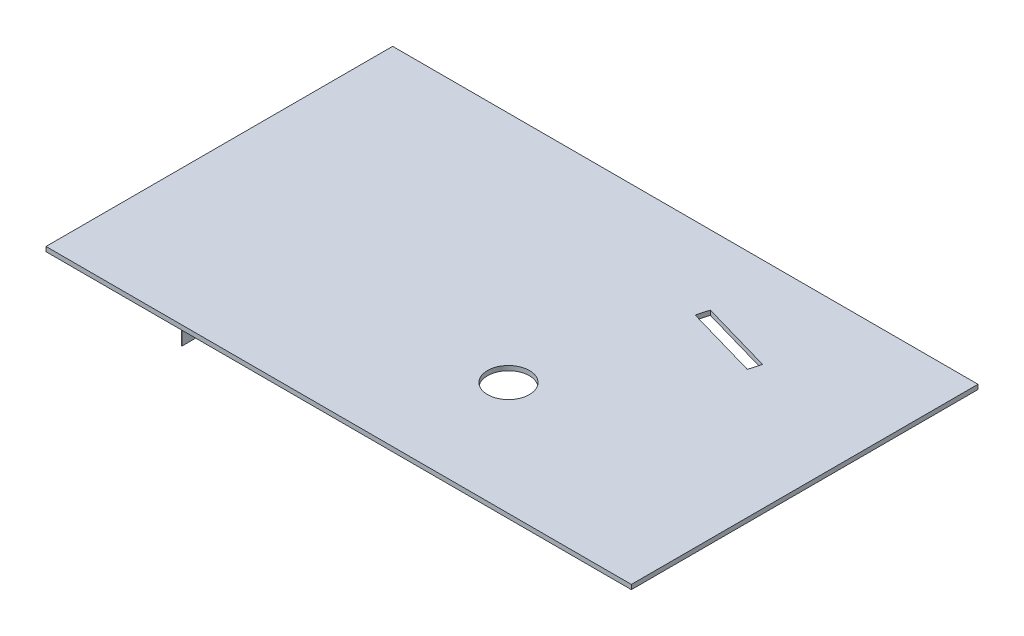
SolidWorks part; units mm, degrees
material "Particle Board"
ref_plane "Front Plane" through (0, 0, 0) normal (0, 0, 1) x (1, 0, 0)
ref_plane "Top Plane" through (0, 0, 0) normal (0, 1, 0) x (1, 0, 0)
ref_plane "Right Plane" through (0, 0, 0) normal (1, 0, 0) x (0, 0, -1)
sketch "Sketch3" plane through (0, 0, 0) normal (0, 1, 0) x (1, 0, 0)
  line L1 (0, 0) -> (-839.8654, 0) construction
  line L2 (0, 0) -> (-451.1992, 260.5) construction
  line L5 (-524, 0) -> (-525.5875, 0)
  line L6 (277.6777, 444.3772) -> (277.6777, 446.248)
  circle A0 centre (0, 0) radius 254 construction
  arc A3 (277.6777, 444.3772) -> (-524, 0) centre (0, 0) ccw
  arc A4 (277.6777, 446.248) -> (-525.5875, 0) centre (0, 0) ccw
  arc A5 (278.5189, 445.7235) -> (-525.5875, 0) centre (0, 0) ccw construction
  dimension "D1" = 524
  dimension "D2" = 1.5875
  dimension "D4" = 122
  dimension "D5" = 508
  dimension "D3" = 30
extrude "Boss-Extrude1" add sketch "Sketch3" along normal blind 50.8
sketch "Sketch4" plane through (0, 50.8, 0) normal (0, 1, 0) x (1, 0, 0)
  line L5 (-848, 566.7) -> (573.9777, 566.7)
  line L6 (-848, 566.7) -> (-848, -275.4)
  line L7 (-848, -275.4) -> (573.9777, -275.4)
  line L8 (573.9777, 566.7) -> (573.9777, -275.4)
  dimension "D1" = 275.4
  dimension "D2" = 848
  dimension "D3" = 566.7
  dimension "D4" = 296.3
extrude "Boss-Extrude2" add sketch "Sketch4" against normal blind 11.1125
hole_wizard "Ø20.0mm Dowel Hole1" positions "Sketch6" profile "Sketch7" hole size "Ø20.0" standard "ANSI Metric" end condition through all
sketch "Sketch6" plane through (0, 50.8, 0) normal (0, 1, 0) x (1, 0, 0)
  point P0 (0, 0)
sketch "Sketch7" plane through (0, 50.8, 0) normal (1, 0, 0) x (0, 0, 1)
  line L0 (0, 0) -> (0, 50.8)
  line L1 (0, 50.8) -> (50.8, 50.8)
  line L2 (50.8, 50.8) -> (50.8, 0)
  line L5 (50.8, 0) -> (0, 0)
  line L11 (0, -6.35) -> (0, 107.95) construction
  dimension "Thru Hole Dia." = 101.6
  dimension "Thru Hole Depth" = 50.8
ref_plane "Plane1" through (0, 0, 269.05) normal (0, 0, 1) x (1, 0, 0)
sketch "Sketch8" plane through (0, 0, 0) normal (0, 0, 1) x (1, 0, 0)
  line L0 (-524, 39.6875) -> (-524, 0) construction
  line L1 (-525.5875, 39.6875) -> (-524, 39.6875)
  line L2 (-525.5875, 39.6875) -> (-525.5875, 0)
  line L3 (-525.5875, 0) -> (-524, 0)
  line L4 (-524, 39.6875) -> (-524, 0)
  line L5 (-525.5875, 39.6875) -> (-525.5875, 0) construction
  line L6 (-525.5875, 0) -> (-524, 0) construction
extrude "Boss-Extrude3" add sketch "Sketch8" along normal up to surface (269.05 mm away) up to plane "Plane1"
sketch "Sketch9" plane through (0, 50.8, 0) normal (0, 1, 0) x (1, 0, 0)
  line L0 (270.6691, 346.7379) -> (92.8357, 397.7308)
  line L1 (92.8357, 397.7308) -> (84.5666, 368.8929)
  line L2 (84.5666, 368.8929) -> (262.4, 317.9)
  line L3 (262.4, 317.9) -> (270.6691, 346.7379)
  line L6 (0, 0) -> (573.9777, 0) construction
  line L7 (573.9777, -275.4) -> (573.9777, 566.7) construction
  dimension "D1" = 185
  dimension "D2" = 30
  dimension "D3" = 16
  dimension "D4" = 262.4
  dimension "D5" = 317.9
extrude "Cut-Extrude1" cut sketch "Sketch9" against normal through all
sketch "Sketch10" plane through (0, 39.6875, 0) normal (0, 1, 0) x (1, 0, 0)
  line L0 (0, 0) -> (-545.6, 0) construction
  line L1 (0, 0) -> (277.6777, 444.3772) construction
  line L2 (0, 0) -> (195.5256, 509.3615) construction
  line L3 (0, 0) -> (94.7424, 537.3111) construction
  circle A0 centre (0, 0) radius 545.6 construction
  dimension "D1" = 11
  dimension "D2" = 11
